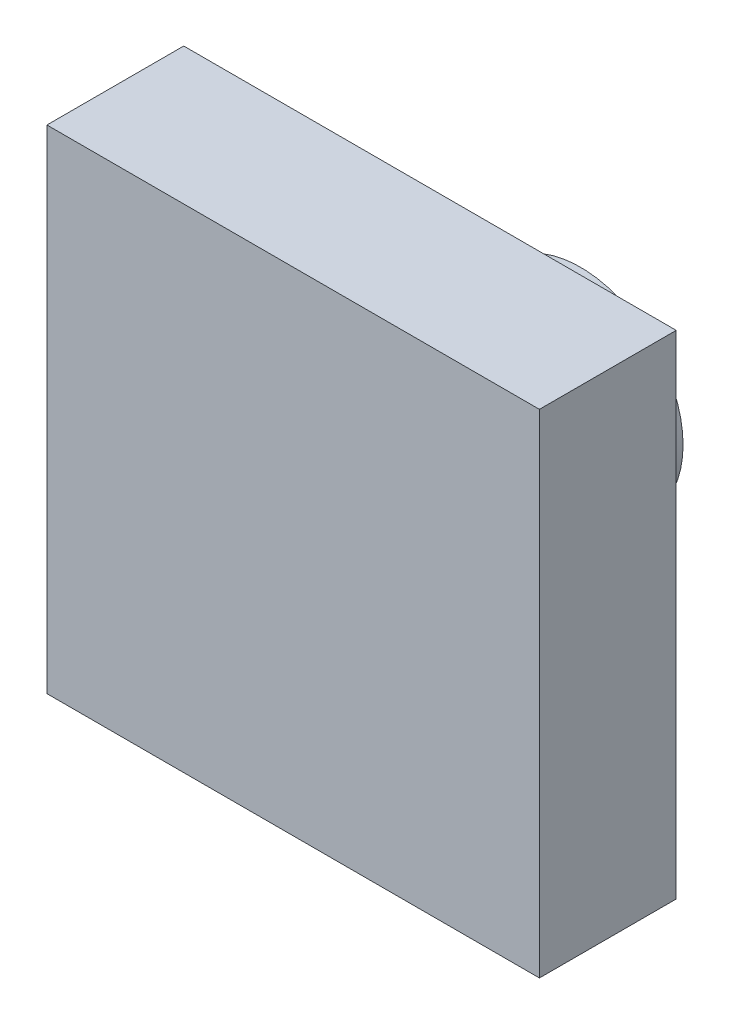
SolidWorks part; units mm, degrees
ref_plane "前视基准面" through (0, 0, 0) normal (0, 0, 1) x (1, 0, 0)
ref_plane "上视基准面" through (0, 0, 0) normal (0, 1, 0) x (1, 0, 0)
ref_plane "右视基准面" through (0, 0, 0) normal (1, 0, 0) x (0, 0, -1)
other "Configuration Table"
sketch "草图1" plane through (0, 0, 0) normal (0, 0, 1) x (1, 0, 0)
  line L1 (18, -18) -> (-18, -18)
  line L2 (18, -18) -> (18, 18)
  line L3 (18, 18) -> (-18, 18)
  line L4 (-18, -18) -> (-18, 18)
  line L5 (18, -18) -> (-18, 18) construction
  line L6 (18, 18) -> (-18, -18) construction
  line L7 (10.8101, -10.8101) -> (-10.8101, -10.8101)
  line L8 (10.8101, -10.8101) -> (10.8101, 10.8101)
  line L9 (10.8101, 10.8101) -> (-10.8101, 10.8101)
  line L10 (-10.8101, -10.8101) -> (-10.8101, 10.8101)
  line L11 (10.8101, -10.8101) -> (-10.8101, 10.8101) construction
  line L12 (10.8101, 10.8101) -> (-10.8101, -10.8101) construction
  point P0 (0, 0)
  point P6 (0, 0)
  dimension "D1" = 36
  dimension "D2" = 36
extrude "凸台-拉伸1" add sketch "草图1" along normal blind 10 contours L10 L7 L8 L9 | L4 L1 L2 L3 L7 L10 L9 L8 region at (0, -17.4909, 0) region at (0, 0, 0)
extrude "凸台-拉伸2" add sketch "草图1<3>" against normal blind 3 contours L10 L7 L8 L9 region at (0, 0, 0)
sketch "草图1<3>" plane through (0, 0, 0) normal (0, 0, 1) x (1, 0, 0) same geometry as "草图1"
sketch "草图2" plane through (0, 0, -3) normal (0, 0, -1) x (-1, 0, 0)
  circle A0 centre (0, 0) radius 7.5
  dimension "D1" = 15
extrude "凸台-拉伸3" add sketch "草图2" along normal blind 8
ref_plane "基准面1" through (0, 0, 0) normal (0, 1, 0) x (1, 0, 0)
